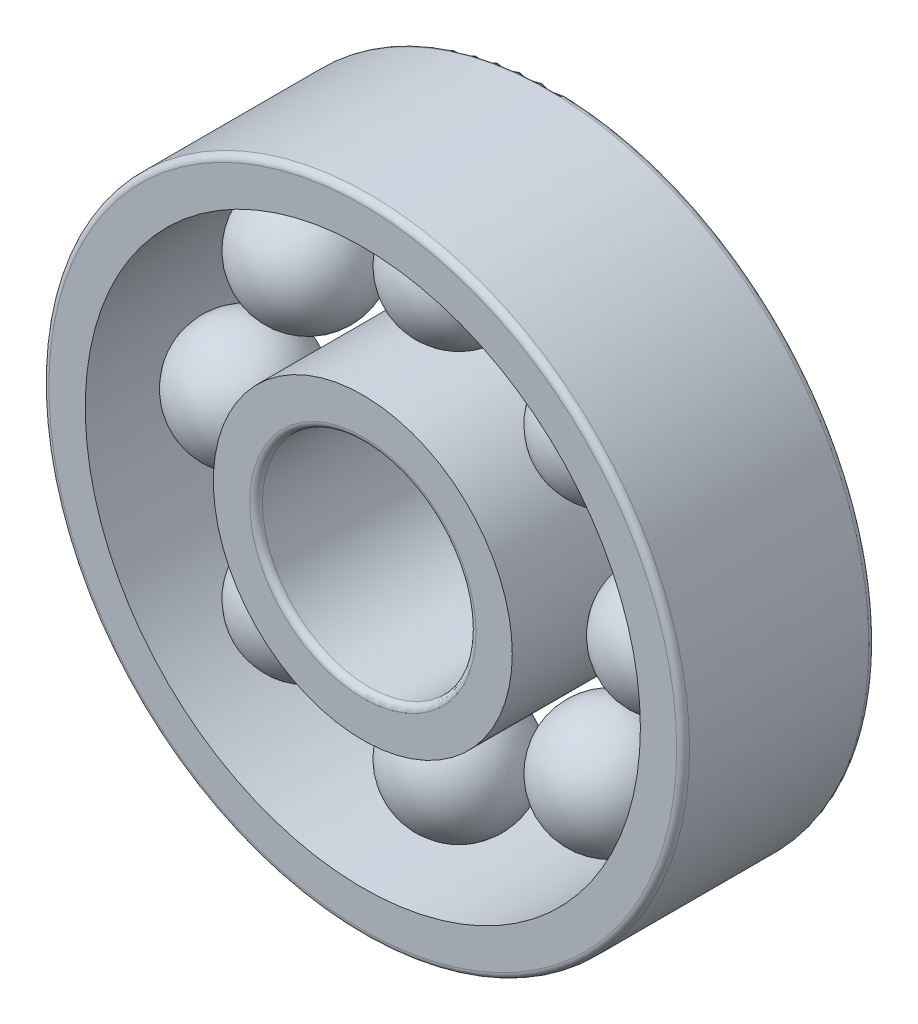
SolidWorks part; units mm, degrees
ref_plane "Front Plane" through (0, 0, 0) normal (0, 0, 1) x (1, 0, 0)
ref_plane "Top Plane" through (0, 0, 0) normal (0, 1, 0) x (1, 0, 0)
ref_plane "Right Plane" through (0, 0, 0) normal (1, 0, 0) x (0, 0, -1)
sketch "S" plane through (0, 0, 0) normal (0, 0, 1) x (1, 0, 0)
  line L0 (-4.5, 0) -> (4.5, 0) construction
  circle A0 centre (0, 0) radius 5 construction
  circle A1 centre (0, 0) radius 15 construction
  circle A2 centre (0, 0) radius 7 construction
  circle A3 centre (0, 0) radius 13 construction
  dimension "ID" = 10
  dimension "OD" = 30
  dimension "IDa" = 14
  dimension "ODa" = 26
  dimension "B" = 9
ref_axis "Z" through (0, 0, -4.95) along (0, 0, 1)
sketch "InnerS" plane through (0, 0, 0) normal (0, 1, 0) x (1, 0, 0)
  line L0 (5, -4.5) -> (7, -4.5)
  line L1 (7, -4.5) -> (7, 4.5)
  line L2 (7, 4.5) -> (5, 4.5)
  line L3 (5, 4.5) -> (5, -4.5)
  line L4 (0, -7.75) -> (0, 7.75) construction
  dimension "r1" = 5
  dimension "r2" = 7
  dimension "z1" = 4.5
  dimension "z2" = 4.5
revolve "InnerRing" add sketch "InnerS" angle 360 about L4
sketch "OuterS" plane through (0, 0, 0) normal (0, 1, 0) x (1, 0, 0)
  line L0 (13, -4.5) -> (15, -4.5)
  line L1 (15, -4.5) -> (15, 4.5)
  line L2 (15, 4.5) -> (13, 4.5)
  line L3 (13, 4.5) -> (13, -4.5)
  line L4 (0, -7.75) -> (0, 7.75) construction
  dimension "r1" = 13
  dimension "r2" = 15
  dimension "z1" = 4.5
  dimension "z2" = 4.5
revolve "OuterRing" add sketch "OuterS" angle 360 about L4
sketch "BallS" plane through (0, 0, 0) normal (0, 1, 0) x (1, 0, 0)
  line L0 (7.15, 0) -> (12.85, 0)
  arc A0 (7.15, 0) -> (12.85, 0) centre (10, 0) ccw
  dimension "r" = 2.85
  dimension "p" = 10
revolve "Ball" add sketch "BallS" angle 360 about L0
pattern_circular "BallsPattern" count 8 over 360 about axis through (0, 0, -4.95) along (0, 0, 1) of bodies 103
fillet "F1" radius 0.3 2 edges at (5, 0, -4.5) (5, 0, 4.5)
fillet "F2" radius 0.3 2 edges at (15, 0, -4.5) (15, 0, 4.5)
equation "\"r1@InnerS\" = abs(0.5*\"ID@S\")"
equation "\"r2@InnerS\" = abs(0.5*\"IDa@S\")"
equation "\"z1@InnerS\" = abs(-0.5*\"B@S\")"
equation "\"z2@InnerS\" = abs(0.5*\"B@S\")"
equation "\"r1@OuterS\" = abs(0.5*\"ODa@S\")"
equation "\"r2@OuterS\" = abs(0.5*\"OD@S\")"
equation "\"z1@OuterS\" = abs(-0.5*\"B@S\")"
equation "\"z2@OuterS\" = abs(0.5*\"B@S\")"
equation "\"r@BallS\" = abs(0.2375*\"ODa@S\"-0.2375*\"IDa@S\")"
equation "\"p@BallS\" = abs(0.25*\"IDa@S\"+0.25*\"ODa@S\")"
equation "\"N@BallsPattern\" = int(2.417*(0.25*\"IDa@S\"+0.25*\"ODa@S\")/(0.2375*\"ODa@S\"-0.2375*\"IDa@S\"))"
equation "\"r_min@F2\" = \"r_min@F1\""
